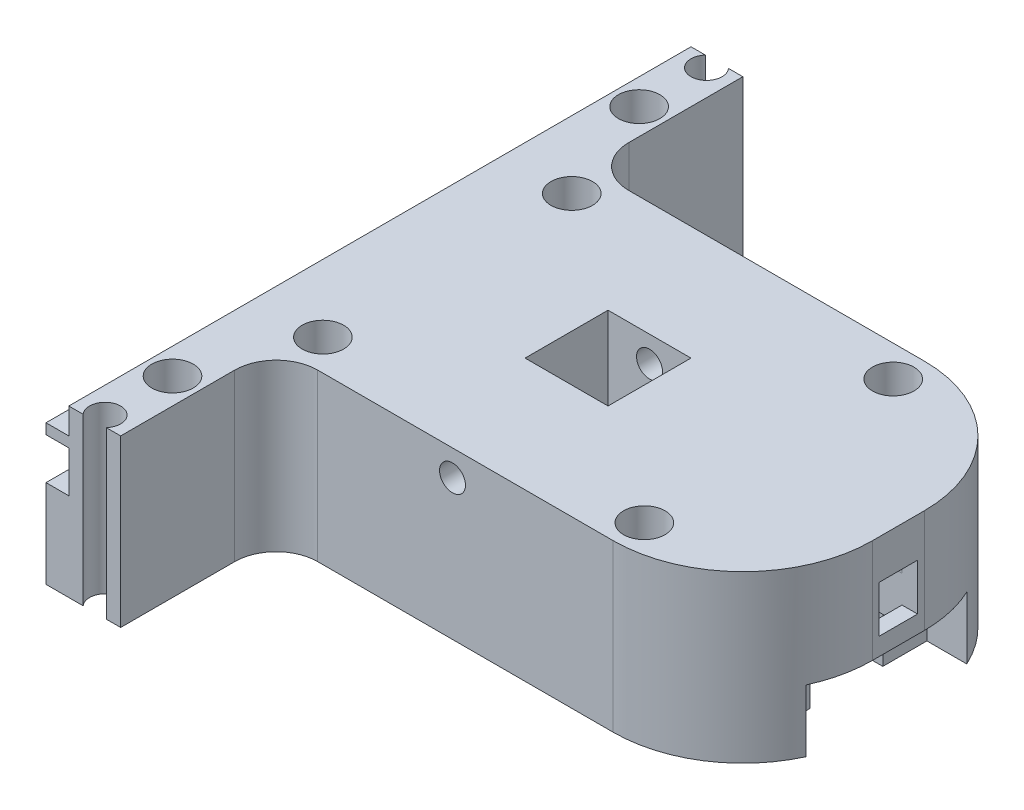
SolidWorks part; units mm, degrees
ref_plane "Front Plane" through (0, 0, 0) normal (0, 0, 1) x (1, 0, 0)
ref_plane "Top Plane" through (0, 0, 0) normal (0, 1, 0) x (1, 0, 0)
ref_plane "Right Plane" through (0, 0, 0) normal (1, 0, 0) x (0, 0, -1)
sketch "Sketch1" plane through (0, 0, 0) normal (0, 0, 1) x (1, 0, 0)
  line L1 (0, 0) -> (18.288, 0)
  line L2 (0, 0) -> (0, 40.64)
  line L3 (0, 40.64) -> (18.288, 40.64)
  line L4 (18.288, 0) -> (18.288, 40.64)
  dimension "D1" = 40.64
  dimension "D2" = 18.288
extrude "Boss-Extrude1" add sketch "Sketch1" along normal blind 152.4
sketch "Sketch2" plane through (0, 0, 0) normal (0, 0, -1) x (-1, 0, 0)
  line L0 (0, 40.64) -> (0, 0) construction
  line L1 (0, 40.64) -> (-5.588, 40.64)
  line L2 (0, 40.64) -> (0, 34.29)
  line L3 (0, 34.29) -> (-5.588, 34.29)
  line L4 (-5.588, 40.64) -> (-5.588, 34.29)
  line L5 (0, 31.75) -> (-5.588, 31.75)
  line L6 (0, 31.75) -> (0, 21.59)
  line L7 (0, 21.59) -> (-5.588, 21.59)
  line L8 (-5.588, 31.75) -> (-5.588, 21.59)
  line L9 (-18.288, 0) -> (-18.288, 40.64) construction
  dimension "D1" = 6.35
  dimension "D2" = 12.7
  dimension "D3" = 12.7
  dimension "D4" = 2.54
  dimension "D5" = 10.16
extrude "Cut-Extrude1" cut sketch "Sketch2" against normal blind 152.4
sketch "Sketch3" plane through (0, 40.64, 0) normal (0, 1, 0) x (1, 0, 0)
  line L0 (11.938, 0) -> (11.938, -152.4) construction
  line L1 (18.288, 0) -> (5.588, 0) construction
  line L2 (18.288, -152.4) -> (5.588, -152.4) construction
  circle A0 centre (11.938, -19.05) radius 5.08
  dimension "D1" = 10.16
  dimension "D2" = 19.05
extrude "Cut-Extrude2" cut sketch "Sketch3" against normal offset from surface (15.24 mm away) 25.4 up to face at (9.144, 0, 76.2)
pattern_linear "LPattern1" count 4 spacing 38.1 along (0, 0, 1) skipping (1, 0), (2, 0) of "Cut-Extrude2"
sketch "Sketch4" plane through (0, 40.64, 0) normal (0, 1, 0) x (1, 0, 0)
  circle A0 centre (11.938, -19.05) radius 2.032
  dimension "D1" = 4.064
extrude "Cut-Extrude3" cut sketch "Sketch4" against normal through all
pattern_linear "LPattern2" count 4 spacing 38.1 along (0, 0, 1) skipping (1, 0), (2, 0) of "Cut-Extrude3"
sketch "Sketch5" plane through (18.288, 0, 0) normal (1, 0, 0) x (0, 0, -1)
  line L0 (-152.4, 40.64) -> (0, 40.64) construction
  line L1 (-114.3, 40.64) -> (-38.1, 40.64)
  line L2 (-114.3, 40.64) -> (-114.3, 0)
  line L3 (-114.3, 0) -> (-38.1, 0)
  line L4 (-38.1, 40.64) -> (-38.1, 0)
  line L5 (-152.4, 0) -> (0, 0) construction
  line L6 (-152.4, 0) -> (-152.4, 40.64) construction
  dimension "D1" = 76.2
  dimension "D2" = 38.1
extrude "Boss-Extrude2" add sketch "Sketch5" along normal blind 114.3
sketch "Sketch6" plane through (0, 40.64, 0) normal (0, 1, 0) x (1, 0, 0)
  line L0 (132.588, -114.3) -> (18.288, -114.3) construction
  line L3 (132.588, -38.1) -> (30.988, -38.1)
  line L6 (132.588, -38.1) -> (132.588, -114.3)
  line L7 (132.588, -114.3) -> (30.988, -114.3)
  line L8 (30.988, -38.1) -> (30.988, -114.3)
  dimension "D1" = 101.6
extrude "Boss-Extrude3" add sketch "Sketch6" along normal blind 22.86
sketch "Sketch8" plane through (0, 40.64, 0) normal (0, 1, 0) x (1, 0, 0)
  line L0 (11.938, -152.4) -> (11.938, 0) construction
  line L1 (18.288, -152.4) -> (5.588, -152.4) construction
  line L2 (18.288, 0) -> (5.588, 0) construction
  circle A0 centre (11.938, -149.86) radius 3.81
  circle A1 centre (11.938, -2.54) radius 3.81
  dimension "D1" = 7.62
  dimension "D3" = 7.62
  dimension "D2" = 2.54
  dimension "D4" = 2.54
extrude "Cut-Extrude5" cut sketch "Sketch8" against normal through all
fillet "Fillet3" radius 10.16 2 edges at (18.288, 20.32, 38.1) (18.288, 20.32, 114.3)
fillet "Fillet4" radius 31.75 2 edges at (132.588, 31.75, 38.1) (132.588, 31.75, 114.3)
sketch "Sketch16" plane through (30.988, 0, 0) normal (-1, 0, 0) x (0, 0, 1)
  line L1 (38.1, 40.64) -> (114.3, 40.64)
  line L2 (38.1, 40.64) -> (38.1, 63.5)
  line L3 (38.1, 63.5) -> (114.3, 63.5)
  line L4 (114.3, 40.64) -> (114.3, 63.5)
extrude "Cut-Extrude13" cut sketch "Sketch16" against normal through all
sketch "Sketch18" plane through (0, 40.64, 0) normal (0, 1, 0) x (1, 0, 0)
  line L0 (5.588, -76.2) -> (132.588, -76.2) construction
  line L1 (51.308, -66.04) -> (71.628, -66.04)
  line L2 (51.308, -66.04) -> (51.308, -86.36)
  line L3 (51.308, -86.36) -> (71.628, -86.36)
  line L4 (71.628, -66.04) -> (71.628, -86.36)
  line L5 (51.308, -66.04) -> (71.628, -86.36) construction
  line L6 (51.308, -86.36) -> (71.628, -66.04) construction
  line L7 (5.588, -152.4) -> (5.588, 0) construction
  line L8 (132.588, -69.85) -> (132.588, -82.55) construction
  point P0 (61.468, -76.2)
  dimension "D1" = 20.32
  dimension "D2" = 20.32
  dimension "D3" = 60.96
extrude "Cut-Extrude14" cut sketch "Sketch18" against normal through all
sketch "Sketch19" plane through (132.588, 0, 0) normal (1, 0, 0) x (0, 0, -1)
  line L0 (-76.2, 15.24) -> (-76.2, 0) construction
  line L1 (-95.885, 0) -> (-56.515, 0)
  line L2 (-95.885, 0) -> (-95.885, 15.24)
  line L3 (-95.885, 15.24) -> (-56.515, 15.24)
  line L4 (-56.515, 0) -> (-56.515, 15.24)
  line L5 (-82.55, 0) -> (-69.85, 0) construction
  point P8 (-76.2, 0)
  dimension "D1" = 39.37
  dimension "D2" = 15.24
extrude "Cut-Extrude15" cut sketch "Sketch19" against normal blind 12.7
sketch "Sketch20" plane through (0, 0, 0) normal (0, -1, 0) x (1, 0, 0)
  line L0 (119.888, 76.2) -> (0, 76.2) construction
  line L1 (119.888, 95.885) -> (119.888, 56.515) construction
  line L2 (0, 152.4) -> (0, 0) construction
  line L4 (81.788, 67.31) -> (119.888, 67.31)
  line L5 (81.788, 67.31) -> (81.788, 85.09)
  line L6 (81.788, 85.09) -> (119.888, 85.09)
  line L7 (119.888, 67.31) -> (119.888, 85.09)
  line L8 (81.788, 67.31) -> (119.888, 85.09) construction
  line L9 (81.788, 85.09) -> (119.888, 67.31) construction
  point P6 (100.838, 76.2)
  dimension "D1" = 17.78
  dimension "D2" = 38.1
extrude "Cut-Extrude16" cut sketch "Sketch20" against normal blind 15.24
sketch "Sketch21" plane through (0, 0, 0) normal (0, -1, 0) x (1, 0, 0)
  line L2 (0, 152.4) -> (0, 0) construction
  line L3 (81.788, 85.09) -> (95.758, 85.09)
  line L4 (81.788, 85.09) -> (81.788, 92.71)
  line L5 (81.788, 92.71) -> (95.758, 92.71)
  line L6 (95.758, 85.09) -> (95.758, 92.71)
  line L7 (95.758, 92.71) -> (0, 92.71)
  line L8 (95.758, 92.71) -> (95.758, 102.87)
  line L9 (95.758, 102.87) -> (0, 102.87)
  line L10 (0, 92.71) -> (0, 102.87)
  line M20 (81.788, 85.09) -> (119.888, 85.09)
  line M30 (0, 152.4) -> (0, 0)
  dimension "D1" = 7.62
  dimension "D2" = 10.16
  dimension "D3" = 13.97
extrude "Cut-Extrude17" cut sketch "Sketch21" against normal blind 15.24 contours L8 L9 L7 L5 M30 | L6 L5 L4 M20 region at (88.773, 0, 88.9) region at (47.879, 0, 97.79)
fillet "Fillet5" radius 10.16 3 edges at (81.788, 7.62, 67.31) (95.758, 7.62, 102.87) (81.788, 7.62, 92.71)
sketch "Sketch22" plane through (132.588, 0, 0) normal (1, 0, 0) x (0, 0, -1)
  line L0 (-76.2, 15.24) -> (-76.2, 40.64) construction
  line L1 (-80.899, 30.988) -> (-71.501, 30.988)
  line L2 (-80.899, 30.988) -> (-80.899, 19.558)
  line L3 (-80.899, 19.558) -> (-71.501, 19.558)
  line L4 (-71.501, 30.988) -> (-71.501, 19.558)
  line L5 (-80.899, 30.988) -> (-71.501, 19.558) construction
  line L6 (-80.899, 19.558) -> (-71.501, 30.988) construction
  line L7 (-69.85, 15.24) -> (-82.55, 15.24) construction
  line L8 (-69.85, 40.64) -> (-82.55, 40.64) construction
  point P0 (-76.2, 25.273)
  dimension "D1" = 11.43
  dimension "D2" = 9.398
  dimension "D3" = 4.318
extrude "Cut-Extrude18" cut sketch "Sketch22" against normal blind 3.81
sketch "Sketch23" plane through (128.778, 0, 0) normal (1, 0, 0) x (0, 0, -1)
  line L0 (-76.2, 30.988) -> (-76.2, 19.558) construction
  line L1 (-71.501, 30.988) -> (-80.899, 30.988) construction
  line L2 (-80.899, 19.558) -> (-71.501, 19.558) construction
  line L4 (-80.899, 26.289) -> (-71.501, 26.289)
  line L5 (-80.899, 26.289) -> (-80.899, 9.779)
  line L6 (-80.899, 9.779) -> (-71.501, 9.779)
  line L7 (-71.501, 26.289) -> (-71.501, 9.779)
  circle A0 centre (-76.2, 26.289) radius 4.699
  line M5 (-71.501, 19.558) -> (-71.501, 30.988)
  line M7 (-80.899, 30.988) -> (-80.899, 19.558)
  line M8 (-80.899, 19.558) -> (-71.501, 19.558)
  dimension "D2" = 9.398
  dimension "D1" = 9.398
  dimension "D3" = 16.51
extrude "Cut-Extrude19" cut sketch "Sketch23" against normal blind 12.7 contours A0 L0 M8 M5 | L4 L0 A0 | A0 L0 L4 | L0 A0 L4 | L0 L4 A0 | L0 A0 M7 M8 | L7 L5 L6 M8 region at (128.778, 28.2833, 74.2057) region at (128.778, 28.2833, 78.1943) region at (128.778, 24.2947, 74.2057) region at (128.778, 24.2947, 78.1943) region at (128.778, 21.2591, 73.4194) region at (128.778, 21.2591, 78.9806) region at (128.778, 14.6685, 76.2)
sketch "Sketch25" plane through (116.078, 0, 0) normal (1, 0, 0) x (0, 0, -1)
  line L1 (-80.899, 15.24) -> (-71.501, 15.24)
  line L2 (-80.899, 15.24) -> (-80.899, 26.289)
  line L3 (-80.899, 26.289) -> (-71.501, 26.289)
  line L4 (-71.501, 15.24) -> (-71.501, 26.289)
revolve "Cut-Revolve1" cut sketch "Sketch25" angle 360 about L1
fillet "Fillet6" radius 12.7 1 edges at (105.029, 15.24, 76.2)
fillet "Fillet7" radius 12.7 3 edges at (0, 7.62, 102.87) (0, 7.62, 92.71) (0, 15.24, 97.79)
sketch "Sketch26" plane through (0, 40.64, 0) normal (0, 1, 0) x (1, 0, 0)
  line L0 (100.838, -38.1) -> (100.838, -114.3) construction
  line L1 (5.588, -76.2) -> (132.588, -76.2) construction
  line L2 (5.588, -152.4) -> (5.588, 0) construction
  line L3 (132.588, -69.85) -> (132.588, -82.55) construction
  line L4 (100.838, -114.3) -> (28.448, -114.3) construction
  line L5 (100.838, -38.1) -> (28.448, -38.1) construction
  circle A0 centre (100.838, -106.68) radius 5.08
  circle A1 centre (100.838, -45.72) radius 5.08
  dimension "D1" = 10.16
  dimension "D2" = 10.16
  dimension "D3" = 7.62
  dimension "D4" = 7.62
extrude "Cut-Extrude20" cut sketch "Sketch26" against normal blind 15.24
sketch "Sketch27" plane through (0, 40.64, 0) normal (0, 1, 0) x (1, 0, 0)
  circle A0 centre (100.838, -106.68) radius 2.032
  circle A1 centre (100.838, -45.72) radius 2.032
  dimension "D1" = 4.064
  dimension "D2" = 4.064
extrude "Cut-Extrude21" cut sketch "Sketch27" against normal through all
ref_plane "Plane1" through (61.468, 0, 0) normal (-1, 0, 0) x (0, 0, 1)
mirror "Mirror1" about plane through (61.468, 0, 0) normal (-1, 0, 0) of "Cut-Extrude20", "Cut-Extrude21"
fillet "Fillet8" radius 10.16 1 edges at (95.758, 7.62, 85.09)
sketch "Sketch29" plane through (0, 0, 38.1) normal (0, 0, -1) x (-1, 0, 0)
  line L0 (-132.588, 15.24) -> (-132.588, 40.64) construction
  line L1 (-100.838, 40.64) -> (-28.448, 40.64) construction
  circle A0 centre (-61.468, 34.29) radius 3.175
  dimension "D1" = 6.35
  dimension "D2" = 71.12
  dimension "D3" = 6.35
extrude "Cut-Extrude22" cut sketch "Sketch29" against normal through all
